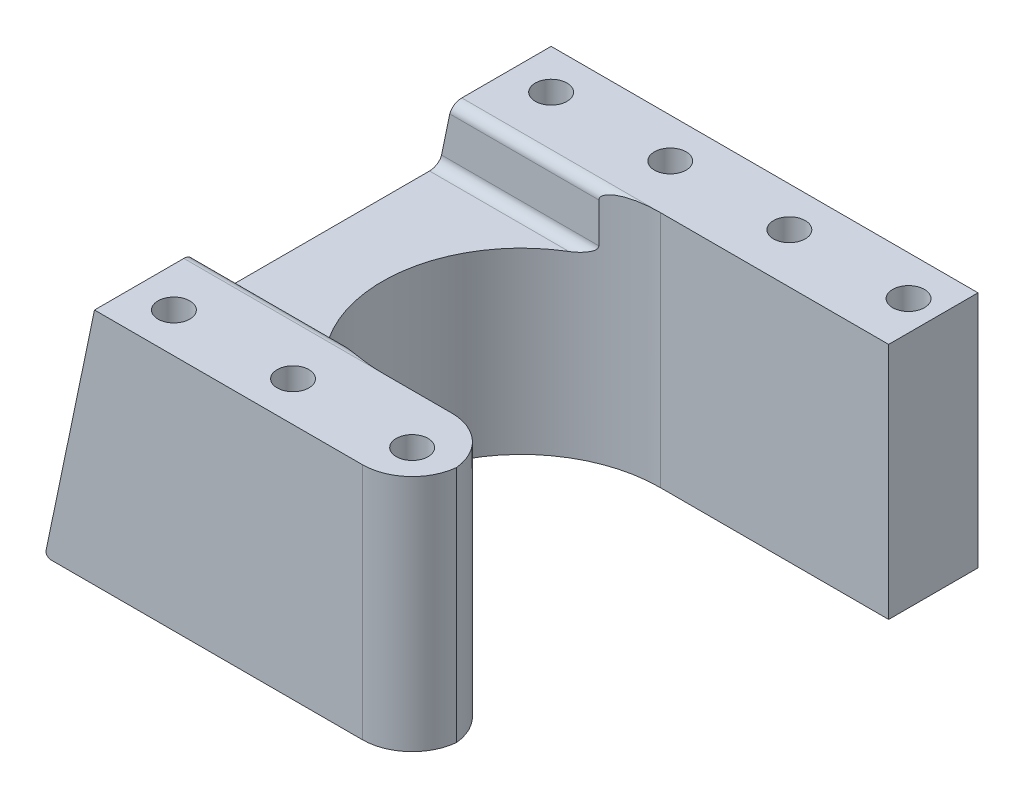
SolidWorks part; units mm, degrees
material "PEI"
ref_plane "Front Plane" through (0, 0, 0) normal (0, 0, 1) x (1, 0, 0)
ref_plane "Top Plane" through (0, 0, 0) normal (0, 1, 0) x (1, 0, 0)
ref_plane "Right Plane" through (0, 0, 0) normal (1, 0, 0) x (0, 0, -1)
sketch "Sketch2" plane through (0, 0, 0) normal (0, 1, 0) x (1, 0, 0)
  line L0 (0, 0) -> (0, 19)
  line L1 (0, 0) -> (-12, 0)
  line L2 (-12, 0) -> (-12, 19)
  line L3 (0, 0) -> (4, 0)
  line L4 (16, -23) -> (-16, -23)
  line L5 (16, -23) -> (16, 23)
  line L6 (16, 23) -> (-16, 23)
  line L7 (-16, -23) -> (-16, 23)
  line L8 (16, -23) -> (-16, 23) construction
  line L9 (16, 23) -> (-16, -23) construction
  line L10 (4, 14) -> (16, 14)
  line L11 (4, -14) -> (16, -14)
  line L12 (12, 19) -> (24.0037, 19)
  line L13 (16, 14) -> (27, 14)
  line L14 (16, 14) -> (16, 23)
  line L15 (16, 23) -> (27, 23)
  line L16 (27, 14) -> (27, 23)
  circle A0 centre (-12, 19) radius 1.6
  circle A1 centre (0, 19) radius 1.6
  circle A2 centre (12, 19) radius 1.6
  circle A4 centre (0, -19) radius 1.6
  circle A5 centre (-12, -19) radius 1.6
  circle A6 centre (4, 0) radius 14
  circle A7 centre (12, -19) radius 1.6
  circle A8 centre (24.0037, 19) radius 1.6
  dimension "D3" = 3.2
  dimension "D4" = 3.2
  dimension "D7" = 28
  dimension "D12" = 3.2
  dimension "D1" = 12
  dimension "D2" = 19
  dimension "D5" = 19
  dimension "D6" = 4
  dimension "D8" = 46
  dimension "D9" = 32
  dimension "D10" = 15
  dimension "D11" = 12.0037
extrude "Boss-Extrude1" add sketch "Sketch2" along normal blind 24 contours A6 L5 L6 L7 L4 A0 A1 A4 A2 A5 | A8 L5 L13 L16 L15 region at (-7.6743, 0, -8.7015) region at (21.2786, 0, -18.4558)
sketch "Sketch4" plane through (0, 0, 23) normal (0, 0, 1) x (1, 0, 0)
  line L0 (-16, 0) -> (-21, 0)
  line L1 (-21, 0) -> (-16, 24)
  line L4 (-16, 0) -> (16, 0)
  line L5 (16, 0) -> (16, 24)
  line L6 (16, 24) -> (-16, 24)
  line L7 (-16, 24) -> (-16, 0)
  line L8 (-16, 0) -> (16, 0)
  line L10 (16, 24) -> (-16, 24)
  line L11 (-16, 24) -> (-16, 0)
  line L14 (16, 0) -> (16, 24)
  line M9 (-16, 24) -> (-16, 0)
  dimension "D2" = 5
  dimension "D1" = 0
extrude "Boss-Extrude2" add sketch "Sketch4" against normal up to surface (46 mm away) contours L1 L0 M9 region at (-17.6667, 8, 23) up to face at (5.5, 12, -23)
sketch "Sketch5" plane through (0, 24, 0) normal (0, 1, 0) x (1, 0, 0)
  line L0 (0, 0) -> (-21, 0)
  line L1 (0, 13) -> (-21, 13)
  line L2 (0, -13) -> (-21, -13)
  line L4 (-16, -23) -> (-16, 23)
  line L5 (-16, 23) -> (-21, 23)
  line L6 (-21, 23) -> (-21, -23)
  line L7 (-21, -23) -> (-16, -23)
  line L8 (-16, -23) -> (-16, 23)
  line L9 (-16, 23) -> (-21, 23)
  line L10 (-21, 23) -> (-21, -23)
  line L11 (-21, -23) -> (-16, -23)
  line L15 (4, 14) -> (27, 14)
  line L16 (16, -23) -> (16, -14)
  line L17 (27, 23) -> (-16, 23)
  line L18 (-16, 23) -> (-16, -23)
  line L19 (-16, -23) -> (16, -23)
  line L20 (27, 14) -> (27, 23)
  line L21 (27, 14) -> (27, 23)
  line L22 (4, 14) -> (27, 14)
  line L23 (16, -23) -> (16, -14)
  line L24 (27, 23) -> (-16, 23)
  line L25 (-16, 23) -> (-16, -23)
  line L26 (-16, -23) -> (16, -23)
  line L30 (16, -14) -> (4, -14)
  line L31 (16, -14) -> (4, -14)
  arc A1 (4, 14) -> (4, -14) centre (4, 0) ccw
  arc A2 (4, 14) -> (4, -14) centre (4, 0) ccw
  arc M16 (4, -14) -> (4, 14) centre (4, 0) cw
  line M20 (-16, 23) -> (-16, -23)
  dimension "D1" = 0
  dimension "D2" = 0
  dimension "D3" = 13
  dimension "D4" = 13
extrude "Cut-Extrude1" cut sketch "Sketch5" against normal blind 6 contours L1 L0 M16 M20 | L1 L10 L0 M20 | L2 L0 M16 M20 | L0 L10 L2 M20 region at (-11.4463, 24, 7.5042) region at (-11.4463, 24, -7.5042) region at (-18.5, 24, 6.5) region at (-18.5, 24, -6.5)
fillet "Fillet1" radius 1 4 edges at (-9.2231, 18, 13) (-9.2231, 18, -13) (-8.5981, 24, 13) (-8.5981, 24, -13)
fillet "Fillet2" radius 0.5 1 edges at (-21, 0, 0)
fillet "Fillet3" radius 5 2 edges at (16, 12, 14) (16, 12, 23)
